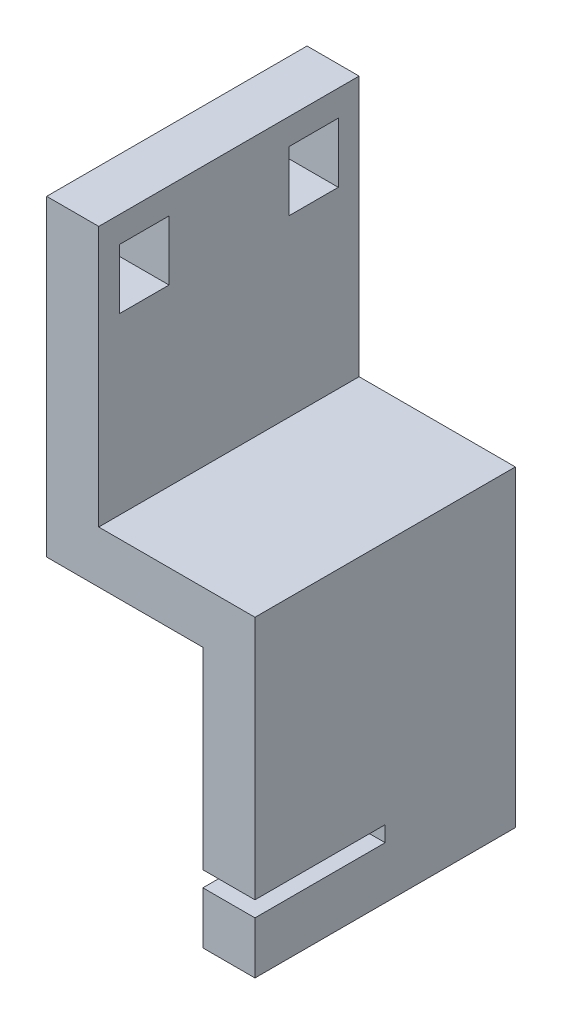
SolidWorks part; units mm, degrees
material "Very Low Density PE (SS)"
ref_plane "Front Plane" through (0, 0, 0) normal (0, 0, 1) x (1, 0, 0)
ref_plane "Top Plane" through (0, 0, 0) normal (0, 1, 0) x (1, 0, 0)
ref_plane "Right Plane" through (0, 0, 0) normal (1, 0, 0) x (0, 0, -1)
sketch "Sketch1" plane through (0, 0, 0) normal (0, 0, 1) x (1, 0, 0)
  line L0 (10, 0) -> (10, 60)
  line L1 (0, 0) -> (0, 50)
  line L2 (0, 50) -> (-30, 50)
  line L3 (-30, 50) -> (-30, 110)
  line L4 (10, 60) -> (-20, 60)
  line L5 (-20, 60) -> (-20, 110)
  line L6 (0, 0) -> (10, 0)
  line L7 (-30, 110) -> (-20, 110)
  line L10 (10, 5) -> (10, 8)
  dimension "D2" = 50
  dimension "D3" = 60
  dimension "D4" = 30
  dimension "D1" = 10
extrude "Boss-Extrude1" add sketch "Sketch1" along normal blind 50 contours L0 L4 L5 L7 L3 L2 L1 L6 region at (-10, 55, 0)
sketch "Sketch2" plane through (10, 0, 0) normal (1, 0, 0) x (0, 0, -1)
  line L0 (-50, 0) -> (-50, 60) construction
  line L1 (-50, 10) -> (-25, 10)
  line L2 (-50, 10) -> (-50, 13)
  line L3 (-50, 13) -> (-25, 13)
  line L4 (-25, 10) -> (-25, 13)
  line L5 (-50, 0) -> (0, 0) construction
  line L6 (-25, 110) -> (-25, 0) construction
  line L7 (-50, 110) -> (0, 110) construction
  dimension "D2" = 3
  dimension "D3" = 10
extrude "Cut-Extrude1" cut sketch "Sketch2" against normal through all
sketch "Sketch3" plane through (-20, 0, 0) normal (1, 0, 0) x (0, 0, -1)
  line L0 (-25, 110) -> (-25, 83.0202) construction
  line L1 (-13.5, 105) -> (-4, 105)
  line L2 (-13.5, 105) -> (-13.5, 93.5)
  line L3 (-13.5, 93.5) -> (-4, 93.5)
  line L4 (-4, 105) -> (-4, 93.5)
  line L5 (-50, 110) -> (0, 110) construction
  line L6 (0, 60) -> (0, 110) construction
  line L8 (-36.5, 93.5) -> (-46, 93.5)
  line L9 (-46, 105) -> (-46, 93.5)
  line L10 (-36.5, 105) -> (-46, 105)
  line L11 (-36.5, 105) -> (-36.5, 93.5)
  dimension "D1" = 11.5
  dimension "D2" = 9.5
  dimension "D3" = 4
  dimension "D4" = 5
extrude "Cut-Extrude2" cut sketch "Sketch3" against normal through all
